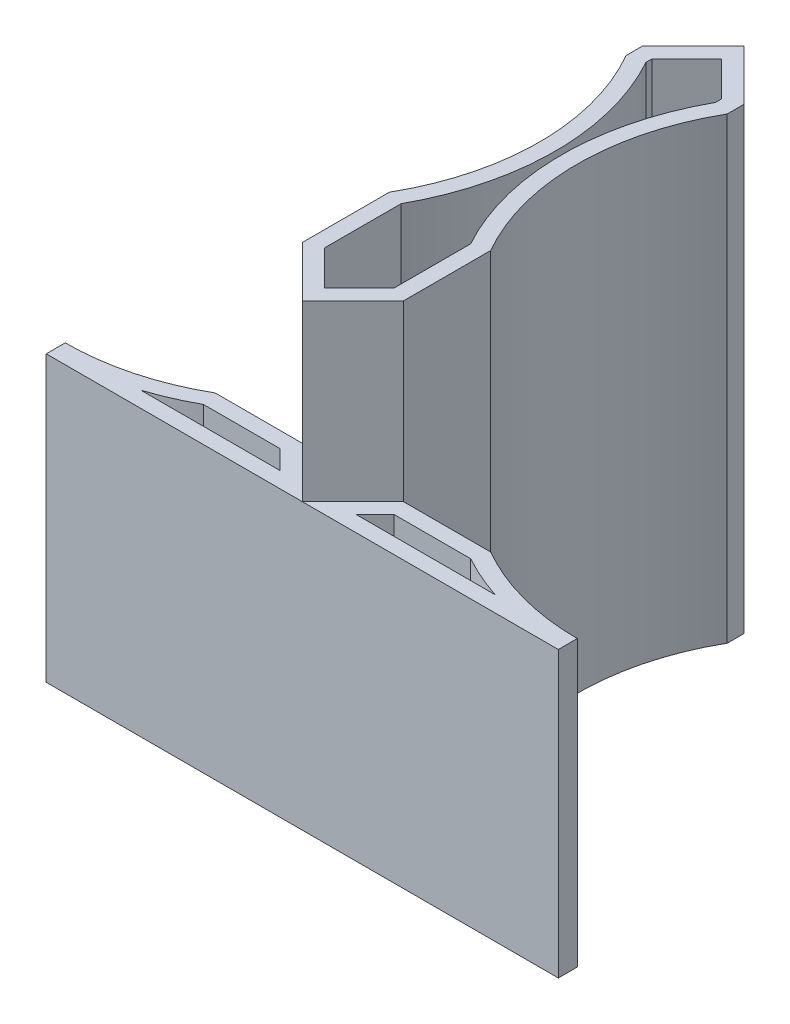
SolidWorks part; units mm, degrees
ref_plane "Front Plane" through (0, 0, 0) normal (0, 0, 1) x (1, 0, 0)
ref_plane "Top Plane" through (0, 0, 0) normal (0, 1, 0) x (1, 0, 0)
ref_plane "Right Plane" through (0, 0, 0) normal (1, 0, 0) x (0, 0, -1)
sketch "Sketch1" plane through (0, 0, 0) normal (0, 1, 0) x (1, 0, 0)
  line L0 (23.7595, 41.275) -> (41.275, 41.275) construction
  line L1 (-41.275, -41.275) -> (-23.7595, -41.275) construction
  line L2 (-41.275, -41.275) -> (-41.275, -23.7595) construction
  line L3 (-41.275, 41.275) -> (-23.7595, 41.275) construction
  line L4 (41.275, -41.275) -> (41.275, -23.7595) construction
  line L5 (-41.275, -41.275) -> (41.275, 41.275) construction
  line L6 (-41.275, 41.275) -> (41.275, -41.275) construction
  line L7 (41.275, 23.7595) -> (41.275, 41.275) construction
  line L8 (-41.275, 23.7595) -> (-41.275, 41.275) construction
  line L9 (23.7595, -41.275) -> (41.275, -41.275) construction
  line L10 (24.7569, 45.085) -> (45.085, 45.085) construction
  line L11 (45.085, 24.7569) -> (45.085, 45.085) construction
  line L12 (45.085, -45.085) -> (45.085, -24.7569) construction
  line L13 (24.7569, -45.085) -> (45.085, -45.085) construction
  line L14 (-45.085, -45.085) -> (-24.7569, -45.085) construction
  line L15 (-45.085, -45.085) -> (-45.085, -24.7569) construction
  line L16 (-45.085, 24.7569) -> (-45.085, 45.085) construction
  line L17 (-45.085, 45.085) -> (-24.7569, 45.085) construction
  line L19 (-51.435, -51.435) -> (51.435, -51.435) construction
  line L20 (-51.435, -51.435) -> (-51.435, 51.435) construction
  line L21 (-51.435, 51.435) -> (51.435, 51.435) construction
  line L22 (51.435, -51.435) -> (51.435, 51.435) construction
  line L23 (-51.435, -51.435) -> (51.435, 51.435) construction
  line L24 (-51.435, 51.435) -> (51.435, -51.435) construction
  arc A1 (-41.275, 23.7595) -> (-41.275, -23.7595) centre (0, 0) ccw construction
  arc A2 (23.7595, 41.275) -> (-23.7595, 41.275) centre (0, 0) ccw construction
  arc A3 (-23.7595, -41.275) -> (23.7595, -41.275) centre (0, 0) ccw construction
  arc A4 (41.275, -23.7595) -> (41.275, 23.7595) centre (0, 0) ccw construction
  arc A5 (45.085, -24.7569) -> (45.085, 24.7569) centre (0, 0) ccw construction
  arc A6 (-24.7569, -45.085) -> (24.7569, -45.085) centre (0, 0) ccw construction
  arc A7 (-45.085, 24.7569) -> (-45.085, -24.7569) centre (0, 0) ccw construction
  arc A8 (24.7569, 45.085) -> (-24.7569, 45.085) centre (0, 0) ccw construction
  point P0 (0, 0)
  dimension "D1" = 82.55
  dimension "D2" = 82.55
  dimension "D3" = 95.25
  dimension "D4" = 3.81
sketch "Sketch2" plane through (0, 0, 0) normal (0, 0, 1) x (1, 0, 0)
  line L0 (0, 48) -> (0, 0) construction
  line L1 (0, 0) -> (0, -9.15) construction
  line L2 (0, 48) -> (0, 82.925) construction
  dimension "Cage height" = 48
  dimension "Plate height" = 34.925
  dimension "D1" = 57.15
  dimension "D2" = 9.15
sketch "Sketch13" plane through (0, 0, 0) normal (0, 1, 0) x (1, 0, 0)
  line L0 (-51.435, -51.435) -> (51.435, -51.435) construction
  line L1 (-41.275, -41.275) -> (-23.7595, -41.275) construction
  line L2 (-41.275, -41.275) -> (-41.275, -23.7595) construction
  line L4 (-51.435, -51.435) -> (0, -51.435)
  line L5 (-41.275, -41.275) -> (-23.7595, -41.275)
  line L6 (-41.275, -41.275) -> (-41.275, -23.7595)
  line L9 (0, -47.625) -> (0, -51.435)
  line L10 (-51.435, 51.435) -> (51.435, -51.435) construction
  line L11 (-41.275, 23.7595) -> (-41.275, 41.275) construction
  line L12 (-51.435, -51.435) -> (-51.435, 51.435) construction
  line L13 (-51.435, 51.435) -> (-41.275, 41.275)
  line L14 (-41.275, 23.7595) -> (-41.275, 41.275)
  line L15 (-51.435, -51.435) -> (-51.435, 51.435)
  arc A0 (-23.7595, -41.275) -> (23.7595, -41.275) centre (0, 0) ccw construction
  arc A2 (-23.7595, -41.275) -> (0, -47.625) centre (0, 0) ccw
  arc A4 (-41.275, 23.7595) -> (-41.275, -23.7595) centre (0, 0) ccw construction
  arc A5 (-41.275, 23.7595) -> (-41.275, -23.7595) centre (0, 0) ccw
extrude "Boss-Extrude2" add sketch "Sketch13" along normal up to vertex (82.925 mm away) and the other way up to vertex (9.15 mm away) up to point (0, 82.925, 0) other way up to point (0, -9.15, 0)
sketch "Sketch15" plane through (0, 82.925, 0) normal (0, 1, 0) x (1, 0, 0)
  line L0 (0, 0) -> (-51.435, -51.435)
  line L1 (-51.435, -51.435) -> (0, -51.435)
  line L2 (0, -51.435) -> (0, 0)
  line L3 (-51.435, -51.435) -> (51.435, -51.435) construction
extrude "Cut-Extrude2" cut sketch "Sketch15" against normal up to vertex (34.925 mm away) up to point (0, 48, 0)
mirror "Mirror1" about plane through (-51.435, 82.925, 51.435) normal (1, 0, 0) of "Boss-Extrude2", "Cut-Extrude2"
sketch "Sketch16" plane through (0, -9.15, 0) normal (0, -1, 0) x (1, 0, 0)
  line L1 (-51.435, -51.435) -> (51.435, -51.435) construction
  circle A5 centre (-51.435, -13.335) radius 1.35
  point P0 (0, 0)
  dimension "D1" = 2.7
  dimension "D2" = 38.1
extrude "Cut-Extrude3" cut sketch "Sketch16" against normal blind 31.75
sketch "Sketch17" plane through (0, 82.925, 0) normal (0, 1, 0) x (1, 0, 0)
  line L0 (7.0944, 7.0944) -> (-7.0944, -7.0944)
  line L1 (7.0944, 7.0944) -> (-44.3406, 58.5294)
  line L2 (-7.0944, -7.0944) -> (-51.435, 37.2462)
  line L3 (-44.3406, 58.5294) -> (-51.435, 51.435)
  line L4 (-41.275, -41.275) -> (41.275, 41.275) construction
  line L5 (-61.595, 41.275) -> (-51.435, 51.435) construction
  line L6 (-51.435, -51.435) -> (-51.435, 51.435) construction
  line L7 (-51.435, 7.7321) -> (-51.435, 82.5591) construction
  line L8 (-95.7756, -7.0944) -> (-51.435, 37.2462)
  line L9 (-58.5294, 58.5294) -> (-51.435, 51.435)
  line L10 (-109.9644, 7.0944) -> (-58.5294, 58.5294)
  line L11 (-109.9644, 7.0944) -> (-95.7756, -7.0944)
  dimension "D1" = 20.066
extrude "Cut-Extrude4" cut sketch "Sketch17" against normal through all
sketch "Sketch18" plane through (0, 82.925, 0) normal (0, 1, 0) x (1, 0, 0)
  line L19 (-58.42, -24.5934) -> (-58.42, -39.9599)
  line L20 (-58.42, -39.9599) -> (-51.435, -46.9449)
  line L21 (-51.435, -46.9449) -> (-44.45, -39.9599)
  line L22 (-44.45, -39.9599) -> (-44.45, -24.5934)
  line L27 (-58.42, -24.5934) -> (-58.42, -39.9599)
  line L28 (-58.42, -39.9599) -> (-51.435, -46.9449)
  line L29 (-51.435, -46.9449) -> (-44.45, -39.9599)
  line L30 (-44.45, -39.9599) -> (-44.45, -24.5934)
  line L32 (-62.9101, -44.45) -> (-78.2766, -44.45)
  line L33 (-87.0077, -48.26) -> (-59.1001, -48.26)
  line L34 (-59.1001, -48.26) -> (-62.9101, -44.45)
  line L35 (-62.9101, -44.45) -> (-78.2766, -44.45)
  line L36 (-87.0077, -48.26) -> (-59.1001, -48.26)
  line L37 (-59.1001, -48.26) -> (-62.9101, -44.45)
  line L42 (-24.5934, -44.45) -> (-39.9599, -44.45)
  line L43 (-39.9599, -44.45) -> (-43.7699, -48.26)
  line L44 (-43.7699, -48.26) -> (-15.8623, -48.26)
  line L45 (-24.5934, -44.45) -> (-39.9599, -44.45)
  line L46 (-39.9599, -44.45) -> (-43.7699, -48.26)
  line L47 (-43.7699, -48.26) -> (-15.8623, -48.26)
  line L48 (-44.45, 25.7711) -> (-51.435, 32.7561)
  line L49 (-44.45, 25.7711) -> (-51.435, 32.7561)
  line L50 (-51.435, 32.7561) -> (-58.42, 25.7711)
  line L51 (-51.435, 32.7561) -> (-58.42, 25.7711)
  line L52 (-58.42, 25.7711) -> (-58.42, 24.5934)
  line L53 (-58.42, 25.7711) -> (-58.42, 24.5934)
  line L54 (-44.45, 24.5934) -> (-44.45, 25.7711)
  line L55 (-44.45, 24.5934) -> (-44.45, 25.7711)
  arc A5 (-87.0077, -48.26) -> (-78.2766, -44.45) centre (-102.87, 0) ccw
  arc A7 (-58.42, -24.5934) -> (-58.42, 24.5934) centre (-102.87, 0) ccw
  arc A8 (-44.45, 24.5934) -> (-44.45, -24.5934) centre (0, 0) ccw
  arc A10 (-58.42, -24.5934) -> (-58.42, 24.5934) centre (-102.87, 0) ccw
  arc A11 (-44.45, 24.5934) -> (-44.45, -24.5934) centre (0, 0) ccw
  arc A12 (-87.0077, -48.26) -> (-78.2766, -44.45) centre (-102.87, 0) ccw
  arc A14 (-24.5934, -44.45) -> (-15.8623, -48.26) centre (0, 0) ccw
  arc A15 (-24.5934, -44.45) -> (-15.8623, -48.26) centre (0, 0) ccw
  dimension "D1" = 3.175
  dimension "D2" = 3.175
  dimension "D3" = 3.175
extrude "Cut-Extrude5" cut sketch "Sketch18" against normal up to surface (60.325 mm away) contours A11 L55 L49 L51 L53 A10 L27 L28 L29 L30 region at (-51.435, 82.925, 12.1349) up to face at (-51.435, 22.6, -14.685)
sketch "Sketch22" plane through (0, 0, 0) normal (0, 1, 0) x (1, 0, 0)
  line L0 (-51.435, -51.435) -> (-51.435, 51.435) construction
  line L1 (-51.435, 51.435) -> (51.435, 51.435) construction
  circle A0 centre (-51.435, -12.065) radius 1.85
  dimension "D1" = 3.7
  dimension "D2" = 63.5
extrude "Cut-Extrude7" cut sketch "Sketch22" against normal through all both and the other way through all
sketch "Sketch20" plane through (0, 22.6, 0) normal (0, 1, 0) x (1, 0, 0)
  line L7 (-56.039, 19.685) -> (-46.831, 19.685)
  line L9 (-47.3448, -18.415) -> (-55.5252, -18.415)
  line L24 (-44.45, 24.5934) -> (-44.45, 25.7711)
  line L25 (-44.45, 25.7711) -> (-51.435, 32.7561)
  line L26 (-51.435, 32.7561) -> (-58.42, 25.7711)
  line L27 (-58.42, 25.7711) -> (-58.42, 24.5934)
  line L28 (-58.42, -24.5934) -> (-58.42, -39.9599)
  line L29 (-58.42, -39.9599) -> (-51.435, -46.9449)
  line L30 (-51.435, -46.9449) -> (-44.45, -39.9599)
  line L31 (-44.45, -39.9599) -> (-44.45, -24.5934)
  line L32 (-44.45, 24.5934) -> (-44.45, 25.7711)
  line L33 (-44.45, 25.7711) -> (-51.435, 32.7561)
  line L34 (-51.435, 32.7561) -> (-58.42, 25.7711)
  line L35 (-58.42, 25.7711) -> (-58.42, 24.5934)
  line L36 (-58.42, -24.5934) -> (-58.42, -39.9599)
  line L37 (-58.42, -39.9599) -> (-51.435, -46.9449)
  line L38 (-51.435, -46.9449) -> (-44.45, -39.9599)
  line L39 (-44.45, -39.9599) -> (-44.45, -24.5934)
  arc A0 (-58.42, -24.5934) -> (-58.42, 24.5934) centre (-102.87, 0) ccw construction
  arc A1 (-47.3448, -18.415) -> (-44.45, -24.5934) centre (0, 0) ccw
  arc A5 (-58.42, -24.5934) -> (-58.42, 24.5934) centre (-102.87, 0) ccw construction
  arc A9 (-44.45, 24.5934) -> (-44.45, -24.5934) centre (0, 0) ccw construction
  arc A11 (-44.45, 24.5934) -> (-44.45, -24.5934) centre (0, 0) ccw construction
  arc A13 (-58.42, -24.5934) -> (-58.42, 24.5934) centre (-102.87, 0) ccw
  arc A14 (-44.45, 24.5934) -> (-44.45, -24.5934) centre (0, 0) ccw
  arc A15 (-58.42, -24.5934) -> (-55.5252, -18.415) centre (-102.87, 0) ccw
  arc A16 (-44.45, 24.5934) -> (-46.831, 19.685) centre (0, 0) ccw
  arc A18 (-56.039, 19.685) -> (-58.42, 24.5934) centre (-102.87, 0) ccw
  circle A19 centre (-51.435, 13.335) radius 1.35 construction
  circle A20 centre (-51.435, -12.065) radius 1.85 construction
  dimension "D2" = 6.35
  dimension "D5" = 6.35
  dimension "D1" = 0
extrude "Cut-Extrude9" cut sketch "Sketch18<3>" against normal through all contours L36 L37 L35 A12 | L45 L46 L47 A15
sketch "Sketch18<3>" plane through (0, 82.925, 0) normal (0, 1, 0) x (1, 0, 0) same geometry as "Sketch18"
extrude "Cut-Extrude10" cut sketch "Sketch20" against normal through all
equation "\"tightTol\"= 0.005in"
equation "\"normTol\"= 0.01in"
equation "\"looseTol\"= 0.02in"
equation "\"Cage height@Sketch2\"=48mm"
equation "\"Plate height@Sketch2\"=1.375"
equation "\"D1@Sketch17\"=0.75in+2*\"looseTol\""
equation "\"D1@Sketch22\"=3.7mm"
equation "\"D1@Sketch16\"=2.7mm"
